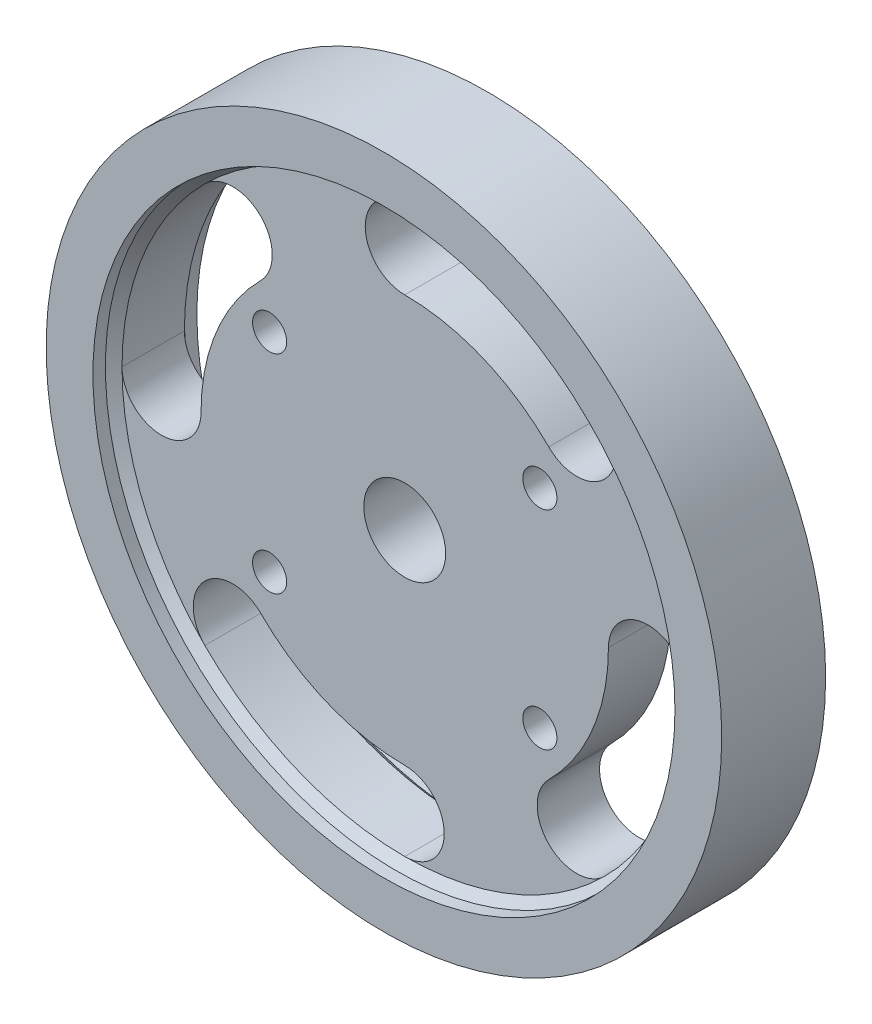
SolidWorks part; units mm, degrees
ref_plane "Front Plane" through (0, 0, 0) normal (0, 0, 1) x (1, 0, 0)
ref_plane "Top Plane" through (0, 0, 0) normal (0, 1, 0) x (1, 0, 0)
ref_plane "Right Plane" through (0, 0, 0) normal (1, 0, 0) x (0, 0, -1)
sketch "Sketch1" plane through (0, 0, 0) normal (0, 0, 1) x (1, 0, 0)
  circle A0 centre (0, 0) radius 20.6375
  dimension "D1" = 41.275
extrude "Base" add sketch "Sketch1" along normal blind 6.35
ref_axis "Axis1" through (0, 0, 19.5503) along (0, 0, -1)
sketch "Sketch3" plane through (0, 0, 0) normal (0, 0, -1) x (-1, 0, 0)
  circle A0 centre (0, 0) radius 3.937
  dimension "D1" = 7.874
extrude "Boss-Extrude2" add sketch "Sketch3" along normal blind 3.81
sketch "Sketch2" plane through (0, 0, 0) normal (0, 0, 1) x (1, 0, 0)
  circle A0 centre (0, 0) radius 2.5
  dimension "D1" = 5
extrude "Cut-Extrude2" cut sketch "Sketch2" along normal through all and the other way through all
sketch "Sketch5" plane through (0, 0, 0) normal (0, 0, 1) x (1, 0, 0)
  line L0 (0, 0) -> (12.2131, 12.2131) construction
  line L1 (0, 0) -> (0, 17.272) construction
  circle A0 centre (0, 0) radius 12.446 construction
  arc A1 (8.8007, 8.8007) -> (0, 12.446) centre (0, 0) ccw
  arc A2 (12.2131, 12.2131) -> (0, 17.272) centre (0, 0) ccw
  arc A3 (8.8007, 8.8007) -> (12.2131, 12.2131) centre (10.5069, 10.5069) ccw
  arc A4 (0, 12.446) -> (0, 17.272) centre (0, 14.859) cw
  dimension "D1" = 24.892
  dimension "D3" = 4.826
  dimension "D2" = 45
extrude "Cut-Extrude3" cut sketch "Sketch5" along normal through all
sketch "Sketch7" plane through (0, 0, 0) normal (0, 0, -1) x (-1, 0, 0)
  circle A0 centre (0, 0) radius 12.446
  circle A1 centre (0, 0) radius 17.78
  arc A2 (0, 12.446) -> (-8.8007, 8.8007) centre (0, 0) ccw construction
  dimension "D1" = 35.56
extrude "Cut-Extrude4" cut sketch "Sketch7" against normal blind 1.27
chamfer "Chamfer1" distance 0.508 angle 45 1 edges at (-17.78, 0, 1.27)
chamfer "Chamfer2" distance 1.27 angle 45 1 edges at (12.446, 0, 0)
chamfer "Chamfer3" distance 0.254 angle 45 1 edges at (-3.937, 0, -3.81)
sketch "Sketch8" plane through (0, 0, 6.35) normal (0, 0, 1) x (1, 0, 0)
  circle A0 centre (0, 0) radius 17.78
  dimension "D1" = 35.56
extrude "Cut-Extrude5" cut sketch "Sketch8" against normal blind 1.27
chamfer "Chamfer4" distance 0.508 angle 45 1 edges at (17.78, 0, 5.08)
sketch "Sketch9" plane through (0, 0, 0) normal (0, 0, -1) x (-1, 0, 0)
  line L1 (-8.255, -6.35) -> (8.255, -6.35) construction
  line L2 (-8.255, -6.35) -> (-8.255, 6.35) construction
  line L3 (-8.255, 6.35) -> (8.255, 6.35) construction
  line L4 (8.255, -6.35) -> (8.255, 6.35) construction
  line L5 (-8.255, -6.35) -> (8.255, 6.35) construction
  line L6 (-8.255, 6.35) -> (8.255, -6.35) construction
  circle A0 centre (-8.255, 6.35) radius 1.0414
  circle A1 centre (8.255, 6.35) radius 1.0414
  circle A2 centre (8.255, -6.35) radius 1.0414
  circle A3 centre (-8.255, -6.35) radius 1.0414
  point P8 (0, 0)
  dimension "D3" = 2.0828
  dimension "D1" = 16.51
  dimension "D2" = 12.7
extrude "Cut-Extrude6" cut sketch "Sketch9" against normal through all
sketch "Sketch10" plane through (0, 0, 0) normal (0, 0, -1) x (-1, 0, 0)
  line L0 (-9.2229, 5.0917) -> (-9.7365, 5.4867)
  line L1 (-10.2295, 5.866) -> (-8.2937, 8.3826)
  line L2 (-9.7365, 5.4867) -> (-10.2295, 5.866)
  line L3 (-7.2871, 7.6083) -> (-7.8006, 8.0033)
  line L4 (-7.8006, 8.0033) -> (-8.2937, 8.3826)
  line L5 (7.2871, 7.6083) -> (7.8006, 8.0033)
  line L6 (8.2937, 8.3826) -> (10.2295, 5.866)
  line L7 (7.8006, 8.0033) -> (8.2937, 8.3826)
  line L8 (9.2229, 5.0917) -> (9.7365, 5.4867)
  line L9 (9.7365, 5.4867) -> (10.2295, 5.866)
  line L10 (9.2229, -5.0917) -> (9.7365, -5.4867)
  line L11 (10.2295, -5.866) -> (8.2937, -8.3826)
  line L12 (9.7365, -5.4867) -> (10.2295, -5.866)
  line L13 (7.2871, -7.6083) -> (7.8006, -8.0033)
  line L14 (7.8006, -8.0033) -> (8.2937, -8.3826)
  line L15 (-7.2871, -7.6083) -> (-7.8006, -8.0033)
  line L16 (-8.2937, -8.3826) -> (-10.2295, -5.866)
  line L17 (-7.8006, -8.0033) -> (-8.2937, -8.3826)
  line L18 (-9.2229, -5.0917) -> (-9.7365, -5.4867)
  line L19 (-9.7365, -5.4867) -> (-10.2295, -5.866)
  arc A0 (-9.2229, 5.0917) -> (-7.2871, 7.6083) centre (-8.255, 6.35) ccw
  arc A1 (-8.3905, -7.3825) -> (-9.2878, -6.2161) centre (-8.255, -6.35) ccw construction
  arc A2 (-9.2878, 6.2161) -> (-9.2878, -6.2161) centre (0, 0) ccw construction
  arc A3 (9.2878, -6.2161) -> (9.2878, 6.2161) centre (0, 0) ccw construction
  arc A4 (8.3905, 7.3825) -> (-8.3905, 7.3825) centre (0, 0) ccw construction
  arc A5 (7.2871, 7.6083) -> (9.2229, 5.0917) centre (8.255, 6.35) ccw
  arc A6 (9.2229, -5.0917) -> (7.2871, -7.6083) centre (8.255, -6.35) ccw
  arc A7 (-7.2871, -7.6083) -> (-9.2229, -5.0917) centre (-8.255, -6.35) ccw
  arc A8 (8.3905, 7.3825) -> (9.2878, 6.2161) centre (8.255, 6.35) ccw construction
  arc A9 (-8.3905, -7.3825) -> (8.3905, -7.3825) centre (0, 0) ccw construction
  arc A10 (9.2878, -6.2161) -> (8.3905, -7.3825) centre (8.255, -6.35) ccw construction
  dimension "D1" = 3.175
  dimension "D4" = 3.175
  dimension "D7" = 3.175
  dimension "D10" = 3.175
  dimension "D2" = 3.175
  dimension "D3" = 1.27
  dimension "D5" = 3.175
  dimension "D6" = 1.27
  dimension "D8" = 3.175
  dimension "D9" = 1.27
  dimension "D11" = 3.175
  dimension "D12" = 1.27
extrude "Cut-Extrude7" cut sketch "Sketch10" against normal blind 0.381
pattern_circular "CirPattern1" count 4 over 360 about axis through (0, 0, 19.5503) along (0, 0, -1) of "Cut-Extrude3"
